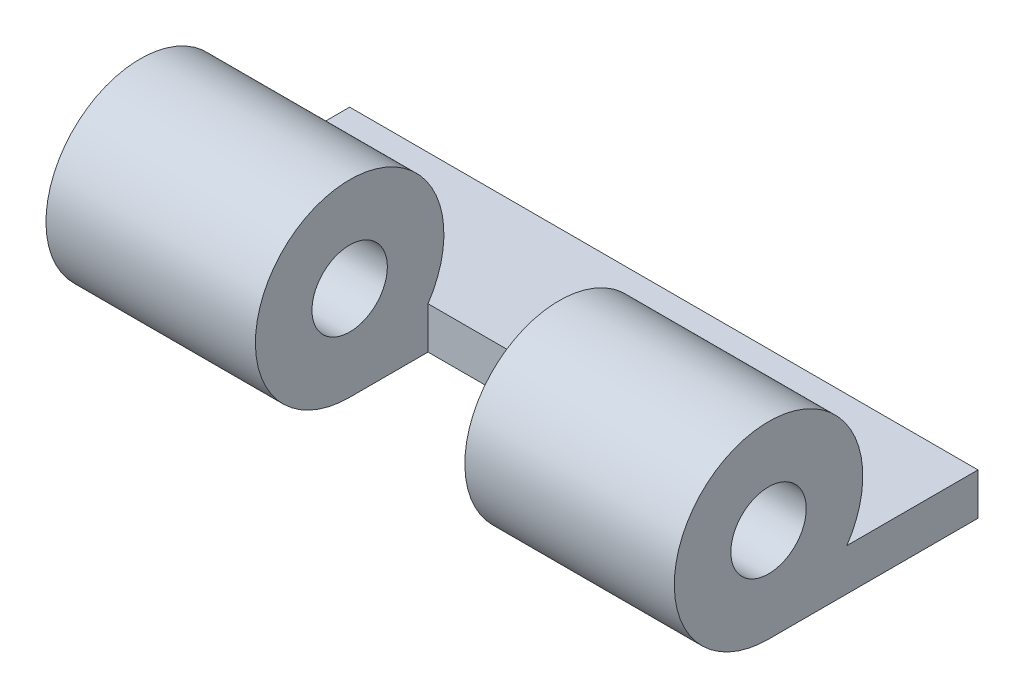
SolidWorks part; units mm, degrees
ref_plane "Ebene vorne" through (0, 0, 0) normal (0, 0, 1) x (1, 0, 0)
ref_plane "Ebene oben" through (0, 0, 0) normal (0, 1, 0) x (1, 0, 0)
ref_plane "Ebene rechts" through (0, 0, 0) normal (1, 0, 0) x (0, 0, -1)
sketch "Skizze2" plane through (0, 0, 0) normal (0, 1, 0) x (1, 0, 0)
  line L1 (-7.5, 2.5) -> (7.5, 2.5)
  line L2 (-7.5, 2.5) -> (-7.5, -2.5)
  line L3 (-7.5, -2.5) -> (7.5, -2.5)
  line L4 (7.5, 2.5) -> (7.5, -2.5)
  line L5 (-7.5, 2.5) -> (7.5, -2.5) construction
  line L6 (-7.5, -2.5) -> (7.5, 2.5) construction
  point P0 (0, 0)
  dimension "D1" = 15
  dimension "D2" = 5
extrude "Aufsatz-Linear austragen1" add sketch "Skizze2" along normal blind 1
sketch "Skizze3" plane through (7.5, 0, 0) normal (1, 0, 0) x (0, 0, -1)
  circle A0 centre (-2.5, 2.25) radius 2.25
  circle A1 centre (-2.5, 2.25) radius 0.9
  dimension "D1" = 1.8
  dimension "D2" = 4.5
extrude "Aufsatz-Linear austragen2" add sketch "Skizze3" against normal up to surface (15 mm away) up to face at (-7.5, 0.5, 0)
ref_plane "Tangential Ebene" through (0, 0, 0.25) normal (0, 0, -1) x (-1, 0, 0)
sketch "Skizze5" plane through (7.5, 0, 0) normal (1, 0, 0) x (0, 0, -1)
  line L0 (-0.6292, 1) -> (-0.6292, 0)
  line L1 (-0.6292, 0) -> (-2.5, 0)
  line L3 (2.5, 1) -> (-0.6292, 1)
  line L4 (-2.5, 0) -> (2.5, 0)
  line L5 (2.5, 0) -> (2.5, 1)
  line L6 (2.5, 1) -> (-0.6292, 1) construction
  line L7 (-2.5, 0) -> (2.5, 0) construction
  line L8 (2.5, 0) -> (2.5, 1) construction
  arc A1 (-0.6292, 1) -> (-2.5, 0) centre (-2.5, 2.25) ccw
  arc A2 (-0.6292, 1) -> (-2.5, 0) centre (-2.5, 2.25) ccw
  dimension "D1" = 0
extrude "Schnitt-Linear austragen1" cut sketch "Skizze5" against normal blind 5 from offset 5 offset against normal yes
